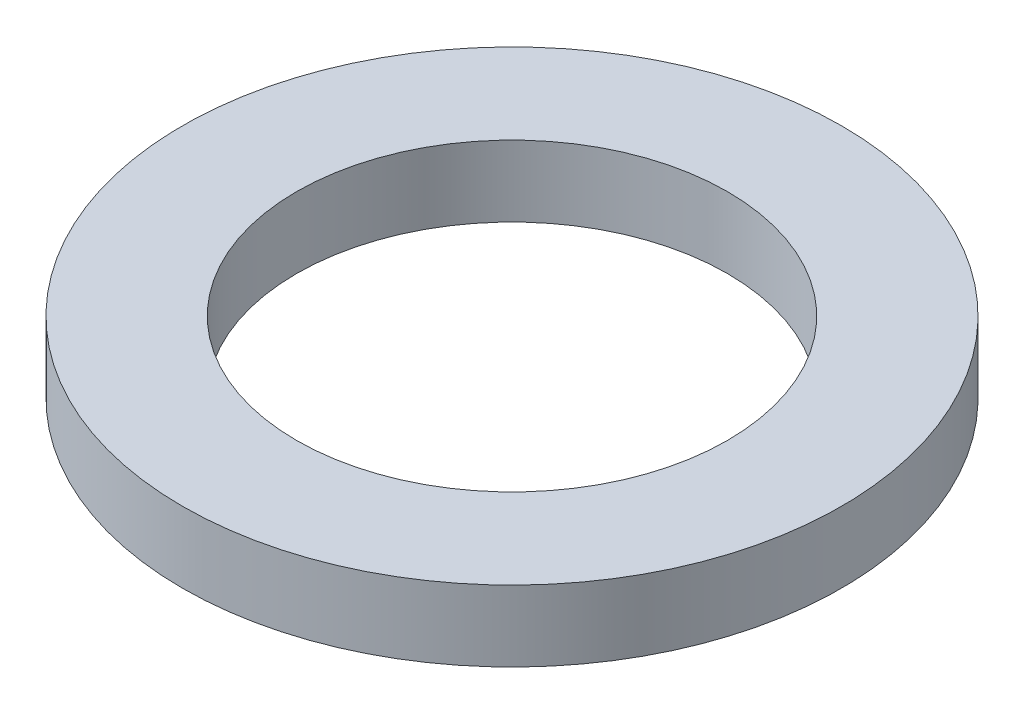
SolidWorks part; units mm, degrees
ref_plane "Front Plane" through (0, 0, 0) normal (0, 0, 1) x (1, 0, 0)
ref_plane "Top Plane" through (0, 0, 0) normal (0, 1, 0) x (1, 0, 0)
ref_plane "Right Plane" through (0, 0, 0) normal (1, 0, 0) x (0, 0, -1)
sketch "Sketch1" plane through (0, 0, 0) normal (0, 1, 0) x (1, 0, 0)
  circle A0 centre (0, 0) radius 65
  dimension "FLANGE_OD" = 130
extrude "Boss-Extrude1" add sketch "Sketch1" along normal blind 14
sketch "Sketch2" plane through (0, 0, 0) normal (0, 1, 0) x (1, 0, 0)
  circle A0 centre (0, 0) radius 42.5
  dimension "BORE_D" = 85
extrude "Cut-Extrude1" cut sketch "Sketch2" along normal through all
sketch "Sketch3" plane through (0, 14, 0) normal (0, 1, 0) x (1, 0, 0)
  circle A0 centre (0, 0) radius 26.8441 construction
  circle A1 centre (-26.8441, 0) radius 3.5849
  dimension "BOLT_D" = 7.1699
  dimension "BOLT_PCD" = 53.6883
extrude "Cut-Extrude2" cut sketch "Sketch3" against normal blind 9.0061 rebuild error yes
pattern_circular "CirPattern1" count 3 over 360 rebuild error yes
